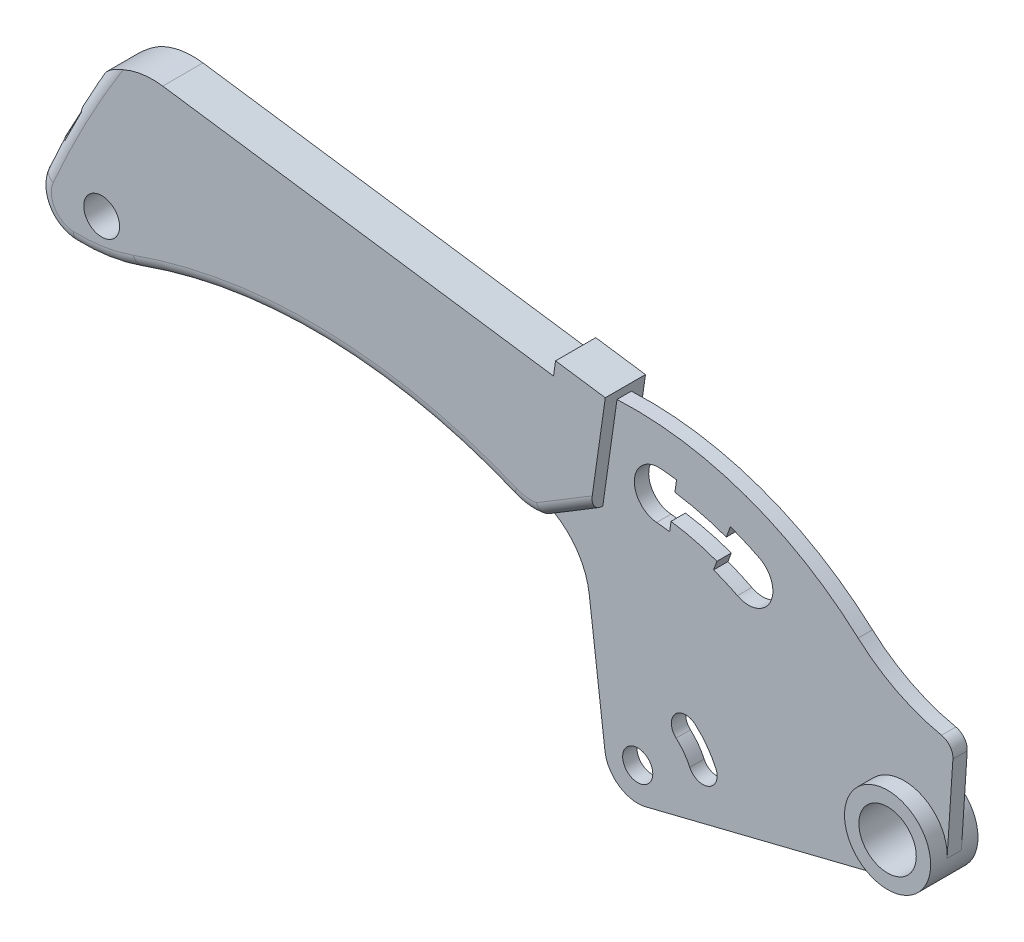
SolidWorks part; units mm, degrees
material "Nylon 101"
ref_plane "Front Plane" through (0, 0, 0) normal (0, 0, 1) x (1, 0, 0)
ref_plane "Top Plane" through (0, 0, 0) normal (0, 1, 0) x (1, 0, 0)
ref_plane "Right Plane" through (0, 0, 0) normal (1, 0, 0) x (0, 0, -1)
sketch "Sketch1" plane through (0, 0, 0) normal (0, 0, 1) x (1, 0, 0)
  line L0 (-177.0524, -42.0271) -> (26.1476, -42.0271) construction
  line L1 (8.636, 15.24) -> (7.6037, -0.4987)
  line L3 (-45.72, -19.2526) -> (1.8434, -7.3937)
  line L4 (-52.9318, -14.296) -> (-55.709, 8.3225)
  line L5 (-128.8945, 50.7525) -> (-59.7444, 40.8895)
  line L6 (-59.7444, 40.8895) -> (-59.3857, 43.404)
  line L7 (-59.3857, 43.404) -> (-50.5848, 42.1487)
  line L8 (-50.5848, 42.1487) -> (-50.8, 40.64)
  line L9 (-45.72, -19.2526) -> (-8.7157, -19.2526) construction
  line L10 (-55.709, 8.3225) -> (-55.709, -14.9131) construction
  arc A1 (8.636, 15.24) -> (6.6237, 17.892) centre (6.1014, 15.4062) ccw
  arc A3 (-8.128, 25.4) -> (-50.8, 40.64) centre (-47.9239, -18.6678) ccw
  arc A5 (1.8434, -7.3937) -> (7.6037, -0.4987) centre (0, 0) ccw
  arc A6 (-45.72, -19.2526) -> (-52.9318, -14.296) centre (-47.1333, -13.5841) cw
  arc A7 (-55.709, 8.3225) -> (-61.976, 17.78) centre (-68.3143, 6.7747) ccw
  arc A8 (-61.976, 17.78) -> (-67.1838, 18.2939) centre (-63.7455, 26.4921) cw
  arc A9 (-67.1838, 18.2939) -> (-133.35, 20.066) centre (-102.549, -66.0303) ccw
  arc A10 (-133.35, 20.066) -> (-144.78, 18.2925) centre (-143.685, 48.9549) cw
  arc A11 (-144.78, 18.2925) -> (-150.3735, 27.178) centre (-144.5534, 24.6385) cw
  arc A12 (-150.3735, 27.178) -> (-141.732, 44.45) centre (18.4086, -46.4686) cw
  arc A13 (-141.732, 44.45) -> (-128.8945, 50.7525) centre (-130.6878, 38.1797) cw
  arc A14 (-8.128, 25.4) -> (6.6237, 17.892) centre (13.1515, 48.9637) ccw
  dimension "D2" = 7.62
  dimension "D4" = 6.35
  dimension "D5" = 91.44
  dimension "D10" = 2.54
  dimension "D13" = 8.89
  dimension "D14" = 12.7
  dimension "D8" = 184.15
  dimension "D19" = 5.842
  dimension "D24" = 31.75
  dimension "D27" = 12.7
  dimension "D1" = 203.2
  dimension "D6" = 61.976
  dimension "D7" = 17.78
  dimension "D9" = 15.24
  dimension "D11" = 133.35
  dimension "D12" = 20.066
  dimension "D15" = 69.85
  dimension "D16" = 50.8
  dimension "D17" = 8.89
  dimension "D18" = 2.54
  dimension "D20" = 14
  dimension "D21" = 141.732
  dimension "D22" = 44.45
  dimension "D23" = 45.72
  dimension "D25" = 40.64
  dimension "D26" = 1.524
  dimension "D28" = 7
  dimension "D29" = 8.636
  dimension "D30" = 25.4
  dimension "D31" = 8.128
  dimension "D32" = 144.78
  dimension "D33" = 27.178
extrude "Boss-Extrude1" add sketch "Sketch1" along normal mid plane 7.112
sketch "Sketch4" plane through (0, 0, 3.556) normal (0, 0, 1) x (1, 0, 0)
  line L0 (-50.8, 40.64) -> (-53.3106, 23.0381)
  line L1 (-53.3106, 23.0381) -> (-61.976, 17.78)
  line L2 (-50.8, 40.64) -> (-50.5848, 42.1487) construction
  line L3 (-55.709, 8.3225) -> (-52.9318, -14.296) construction
  line L4 (-45.72, -19.2526) -> (1.8434, -7.3937) construction
  line L5 (7.6037, -0.4987) -> (8.636, 15.24) construction
  line L6 (-55.709, 8.3225) -> (-52.9318, -14.296)
  line L7 (-45.72, -19.2526) -> (1.8434, -7.3937)
  line L8 (7.6037, -0.4987) -> (8.636, 15.24)
  arc A0 (-55.709, 8.3225) -> (-61.976, 17.78) centre (-68.3143, 6.7747) ccw construction
  arc A1 (-52.9318, -14.296) -> (-45.72, -19.2526) centre (-47.1333, -13.5841) ccw construction
  arc A2 (1.8434, -7.3937) -> (7.6037, -0.4987) centre (0, 0) ccw construction
  arc A3 (8.636, 15.24) -> (6.6237, 17.892) centre (6.1014, 15.4062) ccw construction
  arc A4 (-8.128, 25.4) -> (6.6237, 17.892) centre (13.1515, 48.9637) ccw construction
  arc A5 (-8.128, 25.4) -> (-50.8, 40.64) centre (-47.9239, -18.6678) ccw construction
  arc A6 (-55.709, 8.3225) -> (-61.976, 17.78) centre (-68.3143, 6.7747) ccw
  arc A7 (-52.9318, -14.296) -> (-45.72, -19.2526) centre (-47.1333, -13.5841) ccw
  arc A8 (1.8434, -7.3937) -> (7.6037, -0.4987) centre (0, 0) ccw
  arc A9 (8.636, 15.24) -> (6.6237, 17.892) centre (6.1014, 15.4062) ccw
  arc A10 (-8.128, 25.4) -> (6.6237, 17.892) centre (13.1515, 48.9637) ccw
  arc A11 (-8.128, 25.4) -> (-50.8, 40.64) centre (-47.9239, -18.6678) ccw
  dimension "D1" = 17.78
extrude "Cut-Extrude1" cut sketch "Sketch4" against normal blind 2.286
mirror "Mirror1" about plane through (0, 0, 0) normal (0, 0, 1) of "Cut-Extrude1"
hole_wizard "#97 (0.21) Diameter Hole1" positions "Sketch8" profile "Sketch9" hole size "#97" standard "ANSI Inch" end condition through all
sketch "Sketch8" plane through (0, 0, 1.27) normal (0, 0, 1) x (1, 0, 0)
  point P0 (-47.1333, -13.5841)
sketch "Sketch9" plane through (-47.1333, -13.5841, 1.27) normal (1, 0, 0) x (0, -1, 0)
  line L0 (0, 0) -> (0, 4.826)
  line L1 (0, 4.826) -> (2.667, 4.826)
  line L2 (2.667, 4.826) -> (2.667, 0)
  line L5 (2.667, 0) -> (0, 0)
  line L11 (0, -6.35) -> (0, 107.95) construction
  dimension "Thru Hole Dia." = 5.334
  dimension "Thru Hole Depth" = 4.826
sketch "Sketch10" plane through (0, 0, 0) normal (0, 0, 1) x (1, 0, 0)
  line L0 (-53.3106, 23.0381) -> (-50.5848, 42.1487) construction
  arc A0 (-27.5317, 25.0702) -> (-43.4093, 29.5959) centre (-47.1333, -13.5841) ccw construction
  arc A1 (-25.5787, 28.9214) -> (-43.0382, 33.8979) centre (-47.1333, -13.5841) ccw
  arc A2 (-29.4846, 21.2191) -> (-43.7803, 25.2939) centre (-47.1333, -13.5841) ccw
  arc A3 (-29.4846, 21.2191) -> (-25.5787, 28.9214) centre (-27.5317, 25.0702) ccw
  arc A4 (-43.0382, 33.8979) -> (-43.7803, 25.2939) centre (-43.4093, 29.5959) ccw
  point P4 (-35.253, 28.0961)
  dimension "D1" = 4.318
  dimension "D3" = 43.18
  dimension "D2" = 8.636
  dimension "D4" = 16.51
extrude "Cut-Extrude2" cut sketch "Sketch10" against normal through all both and the other way through all
sketch "Sketch11" plane through (0, 0, 0) normal (0, 0, 1) x (1, 0, 0)
  line L2 (-43.6297, 29.8824) -> (-43.7803, 25.2939) construction
  line L4 (-43.6297, 29.8824) -> (-46.1312, 29.8824) construction
  line L5 (-41.9702, 21.5991) -> (-39.8182, 36.6865)
  line L7 (-34.9026, 19.8064) -> (-29.6609, 34.1166)
  line L9 (-50.8, 40.64) -> (-53.3106, 23.0381) construction
  arc A0 (-29.6609, 34.1166) -> (-39.8182, 36.6865) centre (-47.1333, -13.5841) ccw
  arc A3 (-34.9026, 19.8064) -> (-41.9702, 21.5991) centre (-47.1333, -13.5841) ccw
  circle A4 centre (-47.1333, -13.5841) radius 2.667 construction
  dimension "D1" = 12
  dimension "D2" = 15.24
  dimension "D4" = 50.8
  dimension "D3" = 11.43
extrude "Boss-Extrude2" add sketch "Sketch11" along normal up to surface and the other way up to surface
sketch "Sketch12" plane through (0, 0, 1.27) normal (0, 0, 1) x (1, 0, 0)
  line L0 (-43.4025, 31.8431) -> (-44.0853, 27.0559)
  line L1 (-31.0134, 29.0504) -> (-32.6734, 24.5185)
  line L4 (-40.2618, 33.5762) -> (-41.4813, 25.0267) construction
  line L5 (-33.7117, 23.0574) -> (-30.7414, 31.1665) construction
  arc A0 (-31.0134, 29.0504) -> (-43.4025, 31.8431) centre (-47.1333, -13.5841) ccw
  arc A1 (-32.6734, 24.5185) -> (-44.0853, 27.0559) centre (-47.1333, -13.5841) ccw
  dimension "D1" = 4.826
  dimension "D2" = 12.7
  dimension "D3" = 40.64
  dimension "D4" = 3.048
extrude "Cut-Extrude3" cut sketch "Sketch12" along normal through all both and the other way through all
sketch "Sketch13" plane through (0, 0, 0) normal (0, 0, 1) x (1, 0, 0)
  line L0 (-45.72, -19.2526) -> (1.8434, -7.3937) construction
  arc A0 (-35.6188, -8.2263) -> (-38.6397, -4.1422) centre (-47.1333, -13.5841) ccw construction
  arc A1 (-33.3159, -7.1548) -> (-36.941, -2.2538) centre (-47.1333, -13.5841) ccw
  arc A2 (-37.9217, -9.2979) -> (-40.3385, -6.0306) centre (-47.1333, -13.5841) ccw
  arc A3 (-37.9217, -9.2979) -> (-33.3159, -7.1548) centre (-35.6188, -8.2263) ccw
  arc A4 (-36.941, -2.2538) -> (-40.3385, -6.0306) centre (-38.6397, -4.1422) ccw
  point P4 (-36.923, -6.0317)
  dimension "D3" = 8.255
  dimension "D1" = 5.08
  dimension "D2" = 12.7
  dimension "D4" = 5.08
extrude "Cut-Extrude4" cut sketch "Sketch13" against normal mid plane 2.8448
sketch "Sketch14" plane through (0, 0, 0) normal (0, 0, 1) x (1, 0, 0)
  circle A0 centre (0, 0) radius 7.62
  dimension "D1" = 15.24
extrude "Boss-Extrude3" add sketch "Sketch14" along normal mid plane 8.382
hole_wizard "#97 (0.4) Diameter Hole1" positions "Sketch15" profile "Sketch16" hole size "#97" standard "ANSI Inch" end condition through all
sketch "Sketch15" plane through (0, 0, 4.191) normal (0, 0, 1) x (1, 0, 0)
  point P0 (0, 0)
sketch "Sketch16" plane through (0, 0, 4.191) normal (1, 0, 0) x (0, -1, 0)
  line L0 (0, 0) -> (0, 8.382)
  line L1 (0, 8.382) -> (5.08, 8.382)
  line L2 (5.08, 8.382) -> (5.08, 0)
  line L5 (5.08, 0) -> (0, 0)
  line L11 (0, -6.35) -> (0, 107.95) construction
  dimension "Thru Hole Dia." = 10.16
  dimension "Thru Hole Depth" = 8.382
fillet "Fillet4" radius 2.286 6 edges at (-146.2793, 35.9274, 3.556) (-57.6433, 20.4091, 3.556) (-64.6186, 17.6451, 3.556) (-149.9273, 21.2556, 3.556) (-138.9807, 18.6358, 3.556) (-100.1009, 25.3769, 3.556)
fillet "Fillet5" radius 2.286 5 edges at (-146.2793, 35.9274, -3.556) (-138.9807, 18.6358, -3.556) (-149.9273, 21.2556, -3.556) (-57.6433, 20.4091, -3.556) (-100.1009, 25.3769, -3.556)
hole_wizard "#97 (0.25) Diameter Hole1" positions "Sketch17" profile "Sketch18" hole size "#97" standard "ANSI Inch" end condition through all
sketch "Sketch17" plane through (0, 0, 3.556) normal (0, 0, 1) x (1, 0, 0)
  point P0 (-139.7, 25.4)
  dimension "D1" = 139.7
  dimension "D2" = 25.4
sketch "Sketch18" plane through (-139.7, 25.4, 3.556) normal (1, 0, 0) x (0, -1, 0)
  line L0 (0, 0) -> (0, 7.7762)
  line L1 (0, 7.7762) -> (3.175, 7.7762)
  line L2 (3.175, 7.7762) -> (3.175, 0)
  line L5 (3.175, 0) -> (0, 0)
  line L11 (0, -6.35) -> (0, 107.95) construction
  dimension "Thru Hole Dia." = 6.35
  dimension "Thru Hole Depth" = 7.7762
